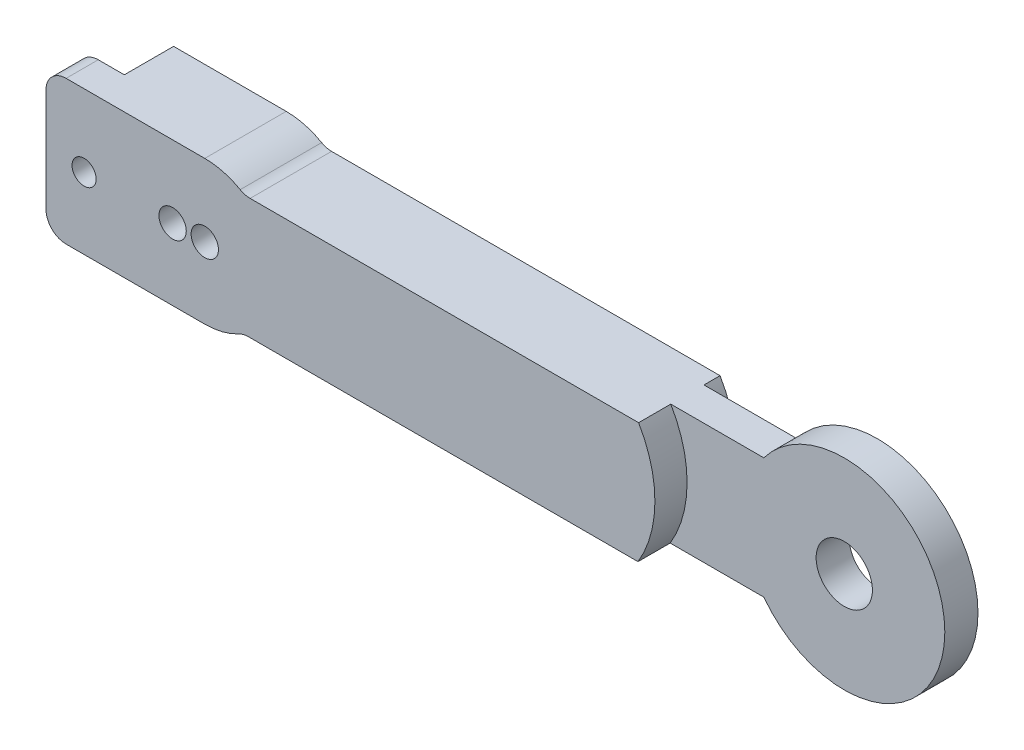
SolidWorks part; units mm, degrees
ref_plane "Front Plane" through (0, 0, 0) normal (0, 0, 1) x (1, 0, 0)
ref_plane "Top Plane" through (0, 0, 0) normal (0, 1, 0) x (1, 0, 0)
ref_plane "Right Plane" through (0, 0, 0) normal (1, 0, 0) x (0, 0, -1)
sketch "Sketch1" plane through (0, 0, 0) normal (0, 0, 1) x (1, 0, 0)
  line L0 (0, 0) -> (14, 0)
  line L1 (14, 7.85) -> (0, 7.85)
  line L2 (0, 7.85) -> (0, 12.85)
  line L3 (0, 12.85) -> (14, 12.85)
  line L4 (14, -5) -> (0, -5)
  line L5 (0, -5) -> (0, 0)
  arc A0 (14, 0) -> (14, 7.85) centre (14, 3.925) ccw
  arc A1 (14, 12.85) -> (14, -5) centre (14, 3.925) cw
  dimension "D1" = 7.85
  dimension "D2" = 14
  dimension "D3" = 5
extrude "Boss-Extrude1" add sketch "Sketch1" along normal blind 4.125
sketch "Sketch2" plane through (0, 0, 0) normal (0, 0, -1) x (-1, 0, 0)
  line L5 (-14, 6.7375) -> (0, 6.7375)
  line L6 (0, -5) -> (0, 0)
  line L7 (0, 0) -> (-14, 0)
  line L8 (-14, 7.85) -> (0, 7.85)
  line L9 (0, 7.85) -> (0, 12.85)
  line L10 (0, 12.85) -> (-14, 12.85)
  line L11 (-14, -5) -> (0, -5)
  line L12 (0, -5) -> (0, 0)
  line L15 (0, 7.85) -> (0, 12.85)
  line L16 (0, 12.85) -> (-14, 12.85)
  line L17 (-14, -5) -> (0, -5)
  line L18 (0, 6.7375) -> (0, 7.85)
  line L19 (-14, 1.1125) -> (0, 1.1125)
  line L20 (0, 1.1125) -> (0, 0)
  arc A1 (-14, 6.7375) -> (-14, 1.1125) centre (-14, 3.925) ccw
  arc A2 (-14, 7.85) -> (-14, 0) centre (-14, 3.925) ccw
  arc A3 (-14, 12.85) -> (-14, -5) centre (-14, 3.925) ccw
  arc A5 (-14, 12.85) -> (-14, -5) centre (-14, 3.925) ccw
  dimension "D2" = 5.625
  dimension "D1" = 0
extrude "Boss-Extrude2" add sketch "Sketch2" along normal blind 2
sketch "Sketch3" plane through (0, 0, 4.125) normal (0, 0, 1) x (1, 0, 0)
  line L1 (0, 12.85) -> (-3.2389, 12.85)
  line L2 (-5.7389, 10.35) -> (-5.7389, -2.5)
  line L3 (-3.2389, -5) -> (0, -5)
  line L6 (0, 0) -> (0, -5)
  line L7 (0, -5) -> (14, -5)
  line L8 (14, 12.85) -> (0, 12.85)
  line L9 (0, 12.85) -> (0, 7.85)
  line L10 (0, 7.85) -> (14, 7.85)
  line L11 (14, 0) -> (0, 0)
  line L13 (0, -5) -> (14, -5)
  line L14 (14, 12.85) -> (0, 12.85)
  line L18 (22.0574, 7.7635) -> (22.0574, 0.0865)
  circle A0 centre (14, 3.8625) radius 1.7
  circle A1 centre (10, 3.8625) radius 1.7
  circle A2 centre (-1, 3.8625) radius 1.5
  arc A3 (22.0574, 7.7635) -> (14, 12.85) centre (14, 3.925) ccw
  arc A4 (14, -5) -> (14, 12.85) centre (14, 3.925) ccw
  arc A5 (14, 0) -> (14, 7.85) centre (14, 3.925) ccw
  arc A6 (14, -5) -> (22.0574, 0.0865) centre (14, 3.925) ccw
  arc A8 (-5.7389, -2.5) -> (-3.2389, -5) centre (-3.2389, -2.5) ccw
  arc A9 (-3.2389, 12.85) -> (-5.7389, 10.35) centre (-3.2389, 10.35) ccw
  dimension "D1" = 3.4
  dimension "D4" = 11
  dimension "D5" = 2.5
  dimension "D2" = 4
  dimension "D3" = 0
extrude "Boss-Extrude3" add sketch "Sketch3" along normal blind 4
sketch "Sketch4" plane through (0, 0, 0) normal (0, 0, 1) x (1, 0, 0)
  line L0 (89.5, 11.3625) -> (18.7216, 11.3625)
  line L1 (89.5, -3.6375) -> (18.7216, -3.6375)
  line L2 (-1, 3.8625) -> (49999, 3.8625) construction
  arc A0 (18.7216, -3.6375) -> (18.7216, 11.3625) centre (14, 3.8625) ccw
  circle A2 centre (-10.5, 3.8625) radius 2.9268 construction
  arc A4 (89.5, 11.3625) -> (89.5, -3.6375) centre (89.5, 3.8625) cw
  dimension "D2" = 100
  dimension "D1" = 15
extrude "Boss-Extrude4" add sketch "Sketch4" along normal up to surface (4.125 mm away) up to face at (22.4912, 3.925, 4.125)
ref_plane "Plane1" through (0, 3.925, 0) normal (0, 1, 0) x (1, 0, 0)
fillet "Fillet2" radius 2.5 2 edges at (18.9335, 11.3625, 2.0625) (18.7396, -3.6375, 2.0625)
sketch "Sketch9" plane through (0, 0, 4.125) normal (0, 0, 1) x (1, 0, 0)
  circle A0 centre (89.5, 3.8625) radius 3.5
  dimension "D1" = 7
extrude "Cut-Extrude1" cut sketch "Sketch9" against normal through all
sketch "Sketch10" plane through (0, 0, 0) normal (0, 0, -1) x (-1, 0, 0)
  circle A0 centre (-89.5, 3.8625) radius 12.5
  circle A1 centre (-89.5, 3.8625) radius 7.5
  dimension "D1" = 25
extrude "Boss-Extrude9" add sketch "Sketch10" against normal up to surface (4.125 mm away) up to face at (93, 3.8625, 4.125)
sketch "Sketch12" plane through (0, 0, 0) normal (0, 0, -1) x (-1, 0, 0)
  line L0 (18.6739, 3.925) -> (-18.6739, 3.925) construction
  line L2 (-19.6371, 11.3625) -> (-79.5, 11.3625)
  line L3 (-79.5, -3.6375) -> (-19.4108, -3.6375)
  line L4 (-19.6371, 11.3625) -> (-67.9318, 11.3625)
  line L5 (-67.8573, -3.6375) -> (-19.4108, -3.6375)
  arc A0 (-67.9318, 11.3625) -> (-67.8573, -3.6375) centre (-55.3075, 3.925) ccw
  arc A4 (-79.5, 11.3625) -> (-79.5, -3.6375) centre (-89.5, 3.8625) ccw
  arc A5 (-18.2268, -3.9356) -> (-19.4108, -3.6375) centre (-19.4108, -6.1375) ccw
  arc A6 (-18.4036, 11.688) -> (-18.2268, -3.9356) centre (-14, 3.925) ccw
  arc A7 (-19.6371, 11.3625) -> (-18.4036, 11.688) centre (-19.6371, 13.8625) ccw
  arc A9 (-18.2268, -3.9356) -> (-19.4108, -3.6375) centre (-19.4108, -6.1375) ccw
  arc A10 (-18.4036, 11.688) -> (-18.2268, -3.9356) centre (-14, 3.925) ccw
  arc A11 (-19.6371, 11.3625) -> (-18.4036, 11.688) centre (-19.6371, 13.8625) ccw
  dimension "D1" = 0
extrude "Boss-Extrude11" add sketch "Sketch12" along normal up to surface (2 mm away) contours L4 A0 L5 A9 A10 A11 up to face at (8.4672, 3.925, -2)
sketch "Sketch13" plane through (0, 0, 4.125) normal (0, 0, 1) x (1, 0, 0)
  line L4 (-3.2389, -5) -> (14, -5)
  line L5 (22.0574, 0.0865) -> (22.0574, 7.7635)
  line L6 (14, 12.85) -> (-3.2389, 12.85)
  line L7 (-5.7389, 10.35) -> (-5.7389, -2.5)
  line L8 (0, -5) -> (14, -5)
  line L9 (0, 1.1125) -> (0, -5)
  line L10 (14, 1.1125) -> (0, 1.1125)
  line L11 (0, 6.7375) -> (14, 6.7375)
  line L12 (0, 12.85) -> (0, 6.7375)
  line L13 (14, 12.85) -> (0, 12.85)
  line L14 (67.9318, 11.3625) -> (19.6371, 11.3625)
  line L15 (19.4108, -3.6375) -> (67.8573, -3.6375)
  line L22 (67.9318, 11.3625) -> (19.6371, 11.3625)
  line L23 (19.4108, -3.6375) -> (67.8573, -3.6375)
  line L25 (22.0574, 0.0865) -> (22.0574, 7.7635)
  arc A4 (14, -5) -> (22.0574, 0.0865) centre (14, 3.925) ccw
  arc A5 (22.0574, 7.7635) -> (14, 12.85) centre (14, 3.925) ccw
  arc A6 (14, 1.1125) -> (14, 6.7375) centre (14, 3.925) ccw
  arc A7 (18.4036, 11.688) -> (14, 12.85) centre (14, 3.925) ccw
  arc A8 (18.4036, 11.688) -> (19.6371, 11.3625) centre (19.6371, 13.8625) ccw
  arc A9 (67.8573, -3.6375) -> (67.9318, 11.3625) centre (55.3075, 3.925) ccw
  arc A10 (19.4108, -3.6375) -> (18.2268, -3.9356) centre (19.4108, -6.1375) ccw
  arc A11 (14, -5) -> (18.2268, -3.9356) centre (14, 3.925) ccw
  arc A14 (18.4036, 11.688) -> (19.6371, 11.3625) centre (19.6371, 13.8625) ccw
  arc A15 (67.8573, -3.6375) -> (67.9318, 11.3625) centre (55.3075, 3.925) ccw
  arc A16 (19.4108, -3.6375) -> (18.2268, -3.9356) centre (19.4108, -6.1375) ccw
  arc A18 (-3.2389, 12.85) -> (-5.7389, 10.35) centre (-3.2389, 10.35) ccw
  arc A19 (-5.7389, -2.5) -> (-3.2389, -5) centre (-3.2389, -2.5) ccw
  arc A20 (18.2268, -3.9356) -> (22.0574, 0.0865) centre (14, 3.925) ccw
  arc A21 (22.0574, 7.7635) -> (18.4036, 11.688) centre (14, 3.925) ccw
  arc A23 (-5.7389, -2.5) -> (-3.2389, -5) centre (-3.2389, -2.5) ccw
  dimension "D1" = 0
  dimension "D2" = 0
extrude "Boss-Extrude12" add sketch "Sketch13" along normal up to surface (4 mm away) contours A14 L22 A15 L23 A16 A20 L25 A21 up to face at (11.7, 3.8625, 8.125)
